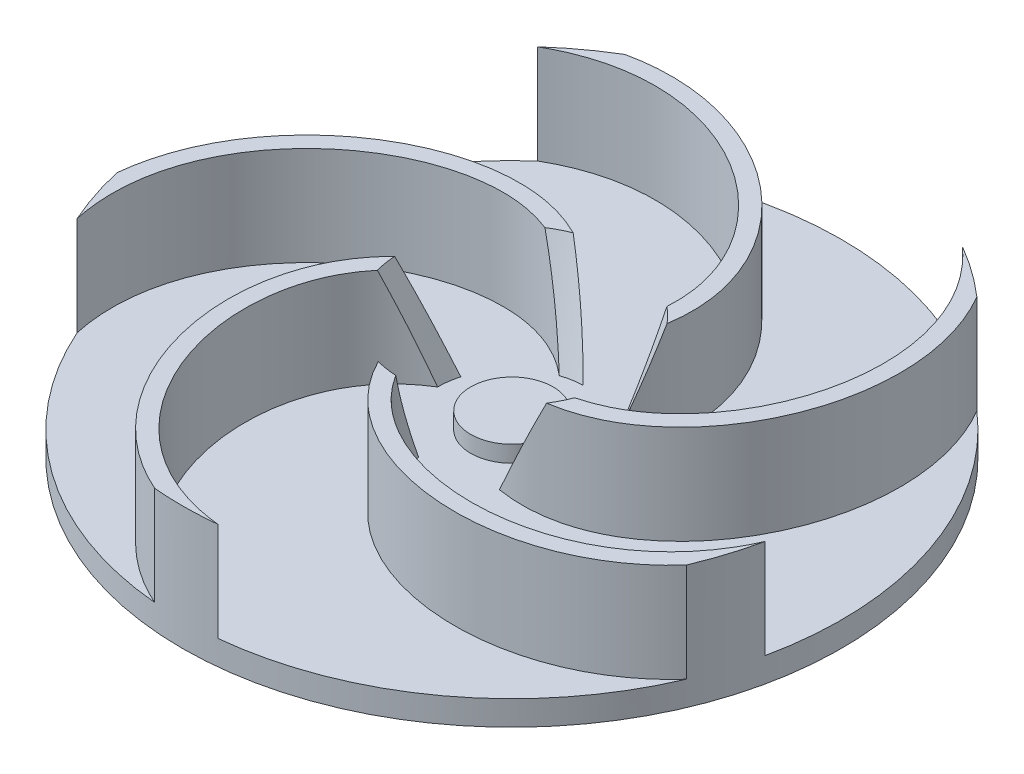
SolidWorks part; units mm, degrees
ref_plane "Front Plane" through (0, 0, 0) normal (0, 0, 1) x (1, 0, 0)
ref_plane "Top Plane" through (0, 0, 0) normal (0, 1, 0) x (1, 0, 0)
ref_plane "Right Plane" through (0, 0, 0) normal (1, 0, 0) x (0, 0, -1)
sketch "Sketch1" plane through (0, 0, 0) normal (0, 1, 0) x (1, 0, 0)
  circle A0 centre (0, 0) radius 40
  dimension "80" = 80
extrude "Boss-Extrude1" add sketch "Sketch1" along normal blind 2 and the other way blind 1
sketch "Sketch2" plane through (0, 2, 0) normal (0, 1, 0) x (1, 0, 0)
  line L0 (-1.6485, 7.4694) -> (-0.2159, 8.865)
  circle A0 centre (0, 0) radius 5
  circle A1 centre (0, 0) radius 40 construction
  spline S0 degree 3 poles (-0.9322, 8.1672) (-16.7296, 24.3832) (-50.3342, 0.2096) (-33.4971, -25.9225) knots 0 0 0 0 1 1 1 1
  spline S1 degree 3 poles (-0.2159, 8.865) (-0.7256, 9.3882) (-1.8191, 10.39) (-4.1049, 12.037) (-7.1913, 13.5227) (-11.1096, 14.412) (-16.4711, 14.5018) (-23.1569, 12.7292) (-30.3764, 8.0968) (-35.0779, 2.5197) (-37.6398, -2.7573) (-38.8535, -7.0652) (-39.2512, -11.6603) (-38.8152, -15.6704) (-37.9571, -18.9511) (-37.0482, -21.4383) (-36.0584, -23.5293) (-35.1262, -25.202) (-34.6046, -26.0499) (-34.3377, -26.4641) knots 0 0 0 0 0.03125 0.0625 0.125 0.1875 0.25 0.375 0.5 0.625 0.6875 0.75 0.8125 0.875 0.90625 0.9375 0.96875 0.984375 1 1 1 1
  spline S2 degree 3 poles (-1.6485, 7.4694) (-2.1049, 7.9379) (-3.0864, 8.837) (-5.1189, 10.3005) (-7.8534, 11.6172) (-11.3437, 12.4111) (-16.1774, 12.4956) (-22.3215, 10.8775) (-29.0387, 6.5707) (-33.4014, 1.3899) (-35.7613, -3.4742) (-36.8743, -7.4268) (-37.2385, -11.6344) (-36.8391, -15.3176) (-36.0462, -18.3506) (-35.2018, -20.6623) (-34.2763, -22.6181) (-33.4006, -24.1898) (-32.9082, -24.9903) (-32.6565, -25.3809) knots 0 0 0 0 0.03125 0.0625 0.125 0.1875 0.25 0.375 0.5 0.625 0.6875 0.75 0.8125 0.875 0.90625 0.9375 0.96875 0.984375 1 1 1 1
  circle M2 centre (0, 0) radius 40
  dimension "D1" = 10
  dimension "D2" = 67.9745
  dimension "D3" = 0.2159
  dimension "D4" = 0.9322
  dimension "D5" = 1.6485
  dimension "D6" = 11.2789
  dimension "D7" = 21.1899
  dimension "D8" = 32.6565
  dimension "D9" = 33.4971
  dimension "D10" = 34.3377
  dimension "D11" = 7.4694
  dimension "D12" = 8.1672
  dimension "D13" = 8.865
  dimension "D14" = 11.9791
  dimension "D15" = 13.2861
extrude "Boss-Extrude2" add sketch "Sketch2" along normal blind 12 contours S2 L0 S0 M2 | L0 S1 S0 M2 region at (-27.0727, 2, -8.2308) region at (-25.7597, 2, -10.2898)
pattern_circular "CirPattern1" count 5 over 360 about axis through (0, 2, 0) along (0, 1, 0) of "Boss-Extrude2"
sketch "Sketch3" plane through (0, 0, 0) normal (0, 0, 1) x (1, 0, 0)
  line L0 (0, 2) -> (-9, 2)
  line L1 (-9, 2) -> (-13.7316, 15)
  line L2 (-13.7316, 15) -> (0, 15)
  line L3 (0, 15) -> (0, 2)
  line L5 (-3.5076, 2) -> (-36.58, 2) construction
  point P3 (0, 0)
  point P8 (-3.5076, 2)
  dimension "D1" = 70
  dimension "D2" = 9
  dimension "D3" = 13
revolve "Cut-Revolve1" cut sketch "Sketch3" angle 360 about L3
sketch "Sketch4" plane through (0, 2, 0) normal (0, 1, 0) x (1, 0, 0)
  circle A0 centre (0, 0) radius 5
  dimension "D1" = 10
extrude "Boss-Extrude3" add sketch "Sketch4" along normal blind 2
